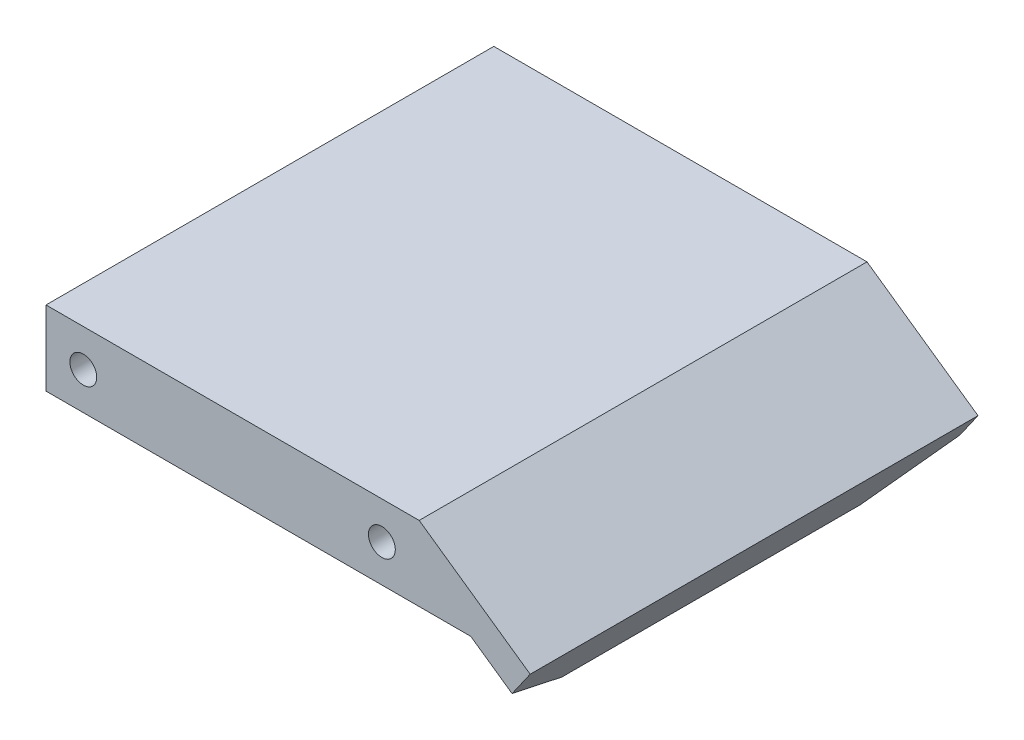
SolidWorks part; units mm, degrees
ref_plane "Front Plane" through (0, 0, 0) normal (0, 0, 1) x (1, 0, 0)
ref_plane "Top Plane" through (0, 0, 0) normal (0, 1, 0) x (1, 0, 0)
ref_plane "Right Plane" through (0, 0, 0) normal (1, 0, 0) x (0, 0, -1)
sketch "Sketch1" plane through (0, 0, 0) normal (0, 0, 1) x (1, 0, 0)
  line L0 (0, 0) -> (63.5, 0)
  line L1 (63.5, 0) -> (82.385, -13.2234)
  line L2 (82.385, -13.2234) -> (75.1006, -23.6266)
  line L3 (75.1006, -23.6266) -> (59.4957, -12.7)
  line L4 (59.4957, -12.7) -> (0, -12.7)
  line L5 (0, -12.7) -> (0, 0)
  dimension "D1" = 12.7
  dimension "D2" = 12.7
  dimension "D3" = 145
  dimension "D4" = 63.5
  dimension "D5" = 19.05
extrude "Boss-Extrude1" add sketch "Sketch1" along normal blind 76.2
sketch "Sketch2" plane through (0, 0, 0) normal (0, 0, -1) x (-1, 0, 0)
  line L1 (0, -12.7) -> (-59.4957, -12.7) construction
  line L2 (0, 0) -> (0, -12.7) construction
  circle A0 centre (-6.35, -6.35) radius 2.286
  dimension "D1" = 4.572
  dimension "D3" = 6.35
  dimension "D2" = 6.35
extrude "Cut-Extrude1" cut sketch "Sketch2" against normal blind 12.7
sketch "Sketch3" plane through (61.4941, -43.0586, 0) normal (0.8192, -0.5736, 0) x (0, 0, -1)
  line L0 (-76.2, 31.0545) -> (-63.5, 23.7221)
  line L1 (-76.2, 23.7221) -> (-76.2, 36.4221) construction
  line L2 (-76.2, 23.7221) -> (0, 23.7221) construction
  line L3 (-63.5, 23.7221) -> (-76.2, 23.7221)
  line L4 (-76.2, 23.7221) -> (-76.2, 31.0545)
  line L5 (-38.1, 36.4221) -> (-38.1, -10.4032) construction
  line L6 (-76.2, 36.4221) -> (0, 36.4221) construction
  line L7 (-76.2, -10.4032) -> (0, -10.4032) construction
  line L8 (-12.7, 23.7221) -> (0, 23.7221)
  line L9 (0, 31.0545) -> (-12.7, 23.7221)
  line L10 (0, 23.7221) -> (0, 31.0545)
  dimension "D1" = 30
  dimension "D2" = 12.7
extrude "Cut-Extrude2" cut sketch "Sketch3" against normal up to surface (19.05 mm away) up to face at (29.7479, -12.7, 38.1)
sketch "Sketch5" plane through (0, 0, 76.2) normal (0, 0, 1) x (1, 0, 0)
  line L0 (0, 0) -> (0, -12.7) construction
  line L1 (63.5, 0) -> (0, 0) construction
  line L2 (0, -12.7) -> (72.2793, -12.7) construction
  circle A0 centre (6.35, -6.35) radius 2.286
  circle A1 centre (57.15, -6.35) radius 2.286
  dimension "D1" = 4.572
  dimension "D2" = 6.35
  dimension "D3" = 6.35
  dimension "D6" = 4.572
  dimension "D4" = 50.8
  dimension "D5" = 6.35
extrude "Cut-Extrude4" cut sketch "Sketch5" against normal through all
